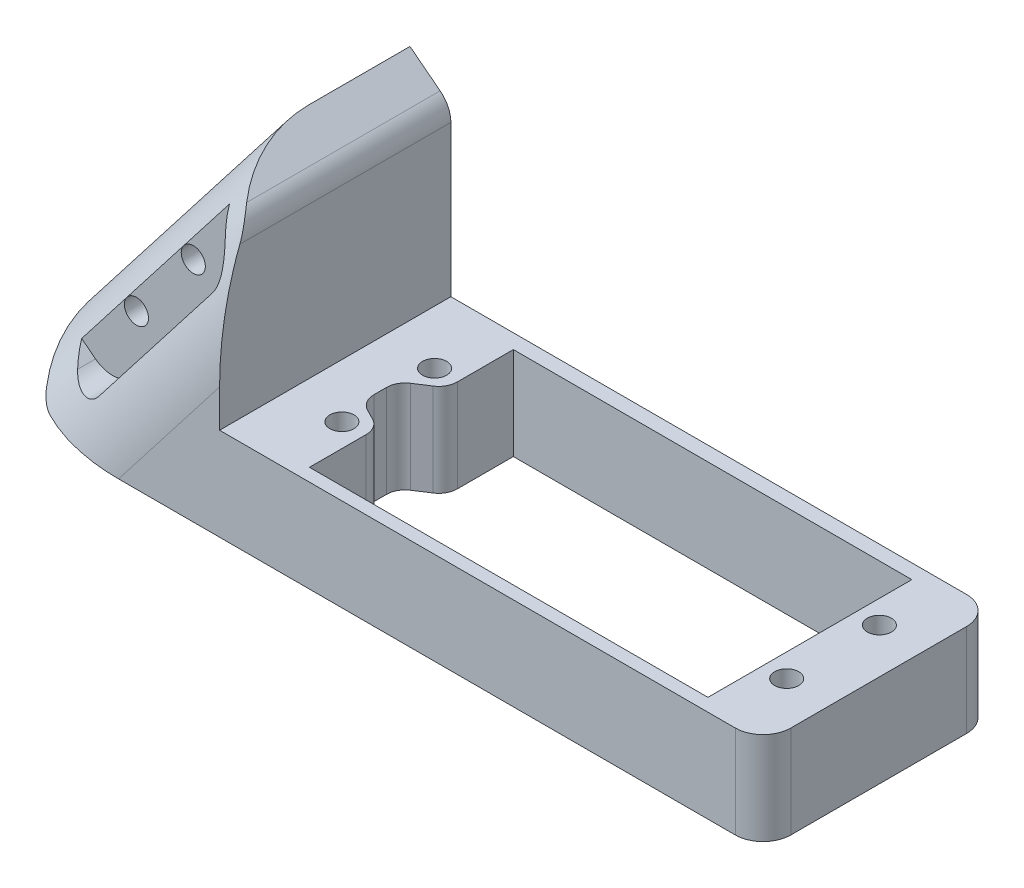
SolidWorks part; units mm, degrees
ref_plane "Alzado" through (0, 0, 0) normal (0, 0, 1) x (1, 0, 0)
ref_plane "Planta" through (0, 0, 0) normal (0, 1, 0) x (1, 0, 0)
ref_plane "Vista lateral" through (0, 0, 0) normal (1, 0, 0) x (0, 0, -1)
sketch "Croquis1" plane through (0, 0, 0) normal (0, 1, 0) x (1, 0, 0)
  line L0 (-10.6555, 24.3386) -> (32.3445, 24.3386)
  line L1 (-10.6555, 24.3386) -> (-10.6555, 2.3386)
  line L2 (-10.6555, 2.3386) -> (32.3445, 2.3386)
  line L3 (32.3445, 24.3386) -> (32.3445, 2.3386)
  line L4 (-17.318, 25.908) -> (39.682, 25.908)
  line L5 (-17.318, 25.908) -> (-17.318, 0.9485)
  line L6 (-17.318, 0.9485) -> (39.682, 0.9485)
  line L7 (39.682, 25.908) -> (39.682, 0.9485)
  dimension "D1" = 43
  dimension "D2" = 22
extrude "Main" add sketch "Croquis1" along normal blind 28
sketch "Croquis2" plane through (0, 0, -0.9485) normal (0, 0, 1) x (1, 0, 0)
  line L0 (-17.318, 28) -> (-17.318, 0) construction
  line L1 (14.682, 30.988) -> (42.6379, 30.988)
  line L2 (14.682, 30.988) -> (14.682, 10)
  line L3 (14.682, 10) -> (42.6379, 10)
  line L4 (42.6379, 30.988) -> (42.6379, 10)
  line L5 (-17.318, 0) -> (39.682, 0) construction
  dimension "D1" = 32
  dimension "D2" = 10
extrude "Corte Caja " cut sketch "Croquis2" against normal up to surface (24.9595 mm away) up to face at (11.182, 14, -25.908)
sketch "Croquis3" plane through (0, 28, 0) normal (0, 1, 0) x (1, 0, 0)
  line L0 (39.682, 25.908) -> (14.682, 25.908) construction
  line L1 (14.682, 25.908) -> (-17.318, 25.908)
  line L2 (14.682, 25.908) -> (14.682, 0.9485)
  line L3 (14.682, 0.9485) -> (-17.318, 0.9485)
  line L4 (-17.318, 25.908) -> (-17.318, 0.9485) construction
  line L6 (16.029, 25.908) -> (26.5297, 25.908) construction
  line L7 (16.029, 24.3386) -> (26.5297, 24.3386) construction
  line L8 (14.682, 24.3386) -> (32.3445, 24.3386) construction
  line L9 (-17.318, 25.908) -> (-17.318, 0.9485)
extrude "Saliente-Extruir2" add sketch "Croquis3" along normal blind 2.25
fillet "Redondeo Laterales" radius 3 2 edges at (39.682, 5, -25.908) (39.682, 5, -0.9485)
sketch "Croquis7" plane through (0, 0, 0) normal (0, -1, 0) x (1, 0, 0)
  line L0 (-18.892, -13.3386) -> (40.144, -13.3386) construction
  line L1 (-18.892, -8.3386) -> (40.144, -8.3386) construction
  line L2 (-18.892, -18.3386) -> (40.6935, -18.3386) construction
  line L3 (-18.2815, -24.3386) -> (39.5335, -24.3386) construction
  line L4 (-10.6555, -2.3386) -> (32.3445, -2.3386) construction
  line L5 (-13.1555, 4.5429) -> (-13.1555, -27.3866) construction
  line L6 (39.7888, 0) -> (39.7888, -27.3866) construction
  line L7 (32.3445, -2.3386) -> (32.3445, -24.3386) construction
  line L8 (34.8445, 2.284) -> (34.8445, -29.5844) construction
  line L9 (-10.6555, -24.3386) -> (-10.6555, -2.3386) construction
  line L11 (36.682, -25.908) -> (-17.318, -25.908) construction
  line L12 (-17.318, -0.9485) -> (36.682, -0.9485) construction
  circle A0 centre (-13.1555, -8.3386) radius 1.3
  circle A1 centre (-13.1555, -18.3386) radius 1.3
  circle A2 centre (34.8445, -8.3386) radius 1.3
  circle A3 centre (34.8445, -18.3386) radius 1.3
  dimension "D7" = 7.5694
  dimension "D1" = 11
  dimension "D2" = 5
  dimension "D3" = 5
  dimension "D4" = 7.4443
  dimension "D5" = 2.5
  dimension "D6" = 2.5
  dimension "D8" = 7.3901
  dimension "D9" = 48
extrude "Taladros Base" cut sketch "Croquis7" against normal blind 11
sketch "Croquis8" plane through (0, 0, 0) normal (0, -1, 0) x (1, 0, 0)
  line L0 (-21.6745, -13.4282) -> (6.4227, -13.4282) construction
  line L1 (-10.6555, -24.3386) -> (-10.6555, -2.3386) construction
  line L2 (-10.6555, -17.1975) -> (-10.6555, -9.6711)
  line L3 (-13.963, -11.3858) -> (-13.963, -15.0595)
  line L4 (-13.963, -15.0595) -> (-10.6555, -17.1975)
  line L5 (-13.963, -11.3858) -> (-10.6555, -9.6711)
  line L6 (-10.6555, -24.3386) -> (-10.6555, -2.3386) construction
extrude "Cajeado cable" cut sketch "Croquis8" against normal blind 10
fillet "Cajeado Redondeo" radius 2 4 edges at (-10.6555, 5, -17.1975) (-13.963, 5, -15.0595) (-13.963, 5, -11.3858) (-10.6555, 5, -9.6711)
sketch "Croquis10" plane through (0, 0, -0.9485) normal (0, 0, 1) x (1, 0, 0)
  line L0 (-17.318, 30.25) -> (-17.318, 0) construction
  line L1 (-17.318, 30.25) -> (-17.318, 0)
  line L2 (-17.318, 0) -> (-40.6979, 0)
  line L3 (-44.719, 3.6985) -> (-22.3543, 32.5027)
  line L4 (-22.3543, 32.5027) -> (-18.0185, 32.5027)
  line L5 (-18.0185, 32.5027) -> (-17.318, 30.25)
  line L6 (-44.719, 3.6985) -> (-40.6979, 0)
extrude "Soporte en angulo" add sketch "Croquis10" against normal up to surface (24.9595 mm away) up to face at (11.3487, 13.4167, -25.908)
sketch "Croquis11" plane through (0, 0, -25.908) normal (0, 0, -1) x (-1, 0, 0)
  line L0 (44.719, 3.6985) -> (22.3543, 32.5027) construction
  line L1 (41.5093, 7.8324) -> (25.564, 28.3688)
  line L2 (42.021, 24.6882) -> (13.7344, 2.7253) construction
  line L3 (21.0849, 21.093) -> (33.3506, 5.2957)
  line L4 (21.6147, 25.3024) -> (25.564, 28.3688)
  line L5 (37.56, 4.766) -> (41.5093, 7.8324)
  arc A0 (33.3506, 5.2957) -> (37.56, 4.766) centre (35.7202, 7.1356) ccw
  arc A1 (21.0849, 21.093) -> (21.6147, 25.3024) centre (23.4545, 22.9328) cw
  point P12 (19.2451, 23.4626)
  dimension "D3" = 3
  dimension "D1" = 13
  dimension "D2" = 8
extrude "Caja para soporte" cut sketch "Croquis11" against normal blind 11
sketch "Croquis12" plane through (0, 0, -14.908) normal (0, 0, -1) x (-1, 0, 0)
  line L0 (21.0849, 21.093) -> (33.3506, 5.2957) construction
  line L1 (21.0849, 21.093) -> (33.3506, 5.2957) construction
  line L2 (39.3229, 22.5599) -> (21.5514, 8.7613) construction
  line L3 (23.5495, 23.7888) -> (37.2567, 6.1349) construction
  circle A0 centre (27.0111, 19.3306) radius 1.3
  circle A1 centre (33.1439, 11.432) radius 1.3
  dimension "D2" = 5
  dimension "D1" = 3.6
  dimension "D3" = 5
extrude "Taladros caja soporte" cut sketch "Croquis12" against normal up to surface (13.9595 mm away) up to face at (-4.4866, 16.5782, -0.9485)
sketch "Croquis15" plane through (0, 0, -0.9485) normal (0, 0, 1) x (1, 0, 0)
  line L0 (14.682, 10) -> (36.682, 10) construction
  line L1 (-18.9664, 10) -> (41.034, 10)
  line L3 (-18.9664, 37.4266) -> (-18.9664, 10)
  line L4 (-18.9664, 37.4266) -> (41.034, 37.4266)
  line L5 (41.034, 37.4266) -> (41.034, 10)
extrude "Recorte Caja" cut sketch "Croquis15" against normal up to surface (24.9595 mm away) up to face at (-14.6721, 16.0733, -25.908)
sketch "Croquis16" plane through (0, 0, -25.908) normal (0, 0, -1) x (-1, 0, 0)
  line L0 (26.0599, 33.2687) -> (17.368, 26.52)
  line L1 (17.368, 26.52) -> (17.368, 33.2687)
  line L2 (17.368, 33.2687) -> (26.0599, 33.2687)
extrude "Chaflan superior soporte" cut sketch "Croquis16" against normal up to surface (24.9595 mm away) up to face at (-34.4439, 11.432, -0.9485)
fillet "Redondeo aristas soporte" radius 3 2 edges at (-40.6979, 0, -13.4282) (-18.9664, 27.7611, -13.4282)
fillet "Redondeo soporte " radius 14 1 edges at (-34.048, 17.442, -0.9485)
sketch "Croquis17" plane through (-29.6911, 23.0534, 0) normal (-0.7899, 0.6133, 0) x (0, 0, 1)
  line L1 (-6.1552, 6.7296) -> (0, 6.7296)
  line L2 (-6.1552, 6.7296) -> (-6.1552, -19.2704)
  line L3 (-6.1552, -19.2704) -> (0, -19.2704)
  line L4 (0, 6.7296) -> (0, -19.2704)
extrude "Caja tornillos soporte" cut sketch "Croquis17" against normal up to surface (8 mm away) up to face at (-27.2177, 13.1944, -20.408)
fillet "redondeo Caja tornillos soporte" radius 3 2 edges at (-35.1904, 2.9261, -4.2273) (-19.2451, 23.4626, -4.2273)
